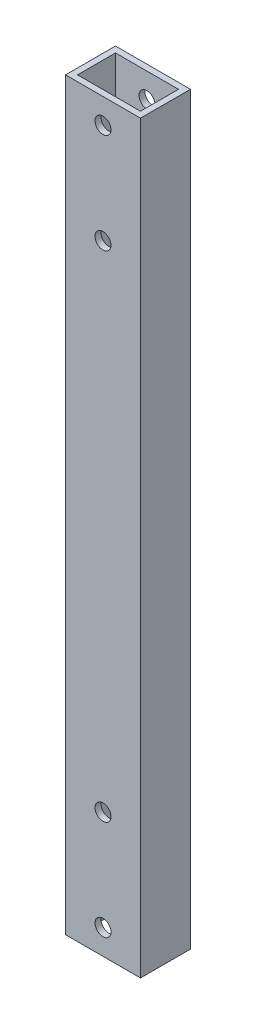
SolidWorks part; units mm, degrees
ref_plane "正面" through (0, 0, 0) normal (0, 0, 1) x (1, 0, 0)
ref_plane "平面" through (0, 0, 0) normal (0, 1, 0) x (1, 0, 0)
ref_plane "右側面" through (0, 0, 0) normal (1, 0, 0) x (0, 0, -1)
sketch "ｽｹｯﾁ1" plane through (0, 0, 0) normal (0, 1, 0) x (1, 0, 0)
  line L0 (-6.3, 3.8) -> (6.3, 3.8)
  line L5 (-7.5, 5) -> (7.5, 5)
  line L6 (-7.5, 5) -> (-7.5, -5)
  line L12 (-7.5, -5) -> (7.5, -5)
  line L13 (7.5, 5) -> (7.5, -5)
  line L14 (-7.5, 5) -> (7.5, -5) construction
  line L15 (-7.5, -5) -> (7.5, 5) construction
  line L16 (6.3, 3.8) -> (6.3, -3.8)
  line L17 (-6.3, -3.8) -> (6.3, -3.8)
  line L18 (-6.3, 3.8) -> (-6.3, -3.8)
  point P0 (0, 0)
  dimension "D1" = 10
  dimension "D2" = 15
  dimension "D3" = 1.2
extrude "ﾎﾞｽ - 押し出し1" add sketch "ｽｹｯﾁ1" along normal mid plane 149.02
sketch "ｽｹｯﾁ3" plane through (0, 0, 5) normal (0, 0, 1) x (1, 0, 0)
  line L0 (0, 74.51) -> (0, 69.51) construction
  line L1 (-7.5, 74.51) -> (7.5, 74.51) construction
  line L2 (0, 69.51) -> (0, 49.51) construction
  circle A0 centre (0, 49.51) radius 1.6
  circle A1 centre (0, 69.51) radius 1.6
  dimension "D3" = 3.2
  dimension "D4" = 3.2
  dimension "D1" = 5
  dimension "D2" = 20
extrude "ｶｯﾄ - 押し出し1" cut sketch "ｽｹｯﾁ3" against normal blind 10
mirror "ﾐﾗｰ1" about plane through (0, 0, 0) normal (0, 1, 0) of "ｶｯﾄ - 押し出し1"
